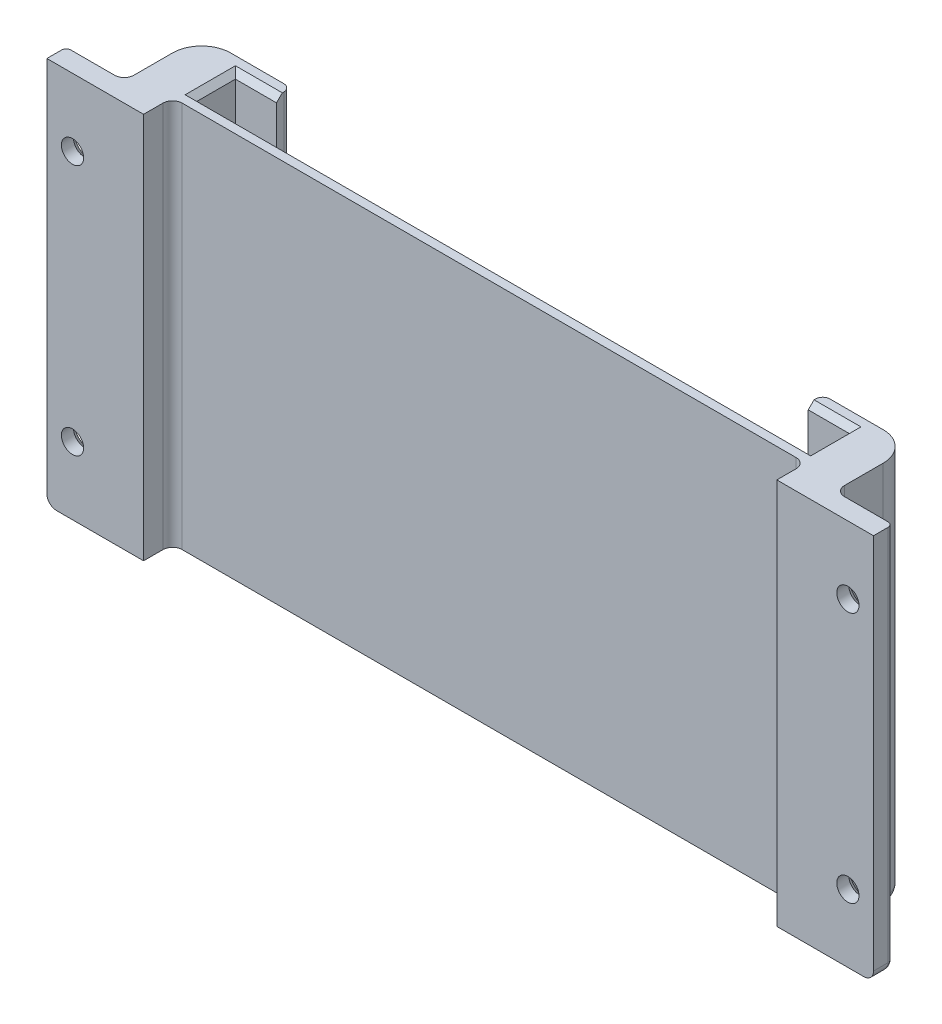
SolidWorks part; units mm, degrees
ref_plane "前视基准面" through (0, 0, 0) normal (0, 0, 1) x (1, 0, 0)
ref_plane "上视基准面" through (0, 0, 0) normal (0, 1, 0) x (1, 0, 0)
ref_plane "右视基准面" through (0, 0, 0) normal (1, 0, 0) x (0, 0, -1)
sketch "草图1" plane through (0, 0, 0) normal (0, 1, 0) x (1, 0, 0)
  line L0 (-85.5, 0) -> (-65.5, 0)
  line L1 (-85.5, 0) -> (-85.5, 4)
  line L2 (-85.5, 4) -> (-73.5, 4)
  line L3 (-73.5, 4) -> (-73.5, 14)
  line L4 (65.5, 0) -> (85.5, 0)
  line L5 (73.5, 14) -> (73.5, 4)
  line L6 (73.5, 4) -> (85.5, 4)
  line L7 (85.5, 4) -> (85.5, 0)
  line L8 (-65.5, 0) -> (-65.5, 4)
  line L9 (-63.5, 6) -> (63.5, 6)
  line L10 (65.5, 4) -> (65.5, 0)
  line L14 (-67.5, 20) -> (67.5, 20)
  arc A0 (-67.5, 20) -> (-73.5, 14) centre (-67.5, 14) ccw
  arc A1 (73.5, 14) -> (67.5, 20) centre (67.5, 14) ccw
  arc A2 (63.5, 6) -> (65.5, 4) centre (63.5, 4) cw
  arc A3 (-65.5, 4) -> (-63.5, 6) centre (-63.5, 4) cw
  point P15 (65.5, 6)
  point P22 (-65.5, 6)
  dimension "D13" = 6
  dimension "D11" = 2
  dimension "D1" = 8
  dimension "D2" = 8
  dimension "D3" = 131
  dimension "D4" = 65.5
  dimension "D5" = 12
  dimension "D6" = 12
  dimension "D7" = 4
  dimension "D8" = 4
  dimension "D9" = 14
  dimension "D10" = 6
extrude "凸台-拉伸1" add sketch "草图1" along normal blind 80
sketch "草图2" plane through (0, 80, 0) normal (0, 1, 0) x (1, 0, 0)
  line L0 (-63.5, 6) -> (63.5, 6) construction
  line L1 (-63.5, 9) -> (63.5, 9)
  line L2 (-63.5, 9) -> (-63.5, 17)
  line L3 (-63.5, 17) -> (63.5, 17)
  line L4 (63.5, 9) -> (63.5, 17)
  line L5 (-63.5, 9) -> (63.5, 17) construction
  line L6 (-63.5, 17) -> (63.5, 9) construction
  line L8 (67.5, 20) -> (-67.5, 20) construction
  point P0 (0, 13)
  dimension "D1" = 8
  dimension "D2" = 3
  dimension "D3" = 127
  dimension "D4" = 63.5
  dimension "D5" = 3
extrude "切除-拉伸1" cut sketch "草图2" against normal blind 70
chamfer "倒角1" distance 1.2 angle 45 4 edges at (63.5, 80, -13) (0, 80, -9) (0, 80, -17) (-63.5, 80, -13)
fillet "圆角1" radius 2 2 edges at (-73.5, 40, -4) (73.5, 40, -4)
fillet "圆角2" radius 1 2 edges at (-85.5, 40, -4) (85.5, 40, -4)
fillet "圆角3" radius 2 13 edges at (85.2071, 0, -3.7071) (-85.2071, 0, -3.7071) (-85.5, 0, -1.5) (85.5, 0, -1.5) (80, 0, -4) (74.0858, 0, -4.5858) (73.5, 0, -10) (71.7426, 0, -18.2426) (0, 0, -20) (-71.7426, 0, -18.2426) (-73.5, 0, -10) (-74.0858, 0, -4.5858) (-80, 0, -4)
sketch "草图3" plane through (0, 0, -20) normal (0, 0, -1) x (-1, 0, 0)
  line L1 (-55, 15) -> (55, 15)
  line L2 (-55, 15) -> (-55, 80)
  line L3 (-55, 80) -> (55, 80)
  line L4 (55, 15) -> (55, 80)
  line L5 (-55, 15) -> (55, 80) construction
  line L6 (-55, 80) -> (55, 15) construction
  line L9 (-67.5, 80) -> (67.5, 80) construction
  point P0 (0, 47.5)
  dimension "D1" = 65
  dimension "D2" = 65
  dimension "D3" = 110
  dimension "D4" = 55
extrude "切除-拉伸2" cut sketch "草图3" against normal blind 3
fillet "圆角5" radius 6 2 edges at (-55, 15, -18.5) (55, 15, -18.5)
fillet "圆角6" radius 1.5 5 edges at (-55, 50.5, -20) (-53.2426, 16.7574, -20) (0, 15, -20) (53.2426, 16.7574, -20) (55, 50.5, -20)
sketch "草图4" plane through (0, 0, -4) normal (0, 0, -1) x (-1, 0, 0)
  line L0 (75.5, 80) -> (84.5, 80) construction
  line L1 (83.5, 0) -> (75.5, 0) construction
  line L2 (-75.5, 0) -> (-83.5, 0) construction
  line L3 (-84.5, 80) -> (-75.5, 80) construction
  line L4 (-85.5, 2) -> (-85.5, 80) construction
  line L5 (85.5, 80) -> (85.5, 2) construction
  circle A0 centre (80.2, 66) radius 2.3
  circle A1 centre (80.2, 14) radius 2.3
  circle A2 centre (-80.2, 14) radius 2.3
  circle A3 centre (-80.2, 66) radius 2.3
  point P8 (80, 80)
  point P13 (-79.5, 0)
  dimension "D1" = 4.6
  dimension "D2" = 14
  dimension "D3" = 14
  dimension "D5" = 14
  dimension "D6" = 5.3
  dimension "D7" = 5.3
  dimension "D8" = 5.3
  dimension "D9" = 5.3
  dimension "D4" = 14
extrude "切除-拉伸3" cut sketch "草图4" against normal blind 4
chamfer "倒角2" distance 1.5 angle 45 4 edges at (77.9, 14, -4) (77.9, 66, -4) (-82.5, 14, -4) (-82.5, 66, -4)
